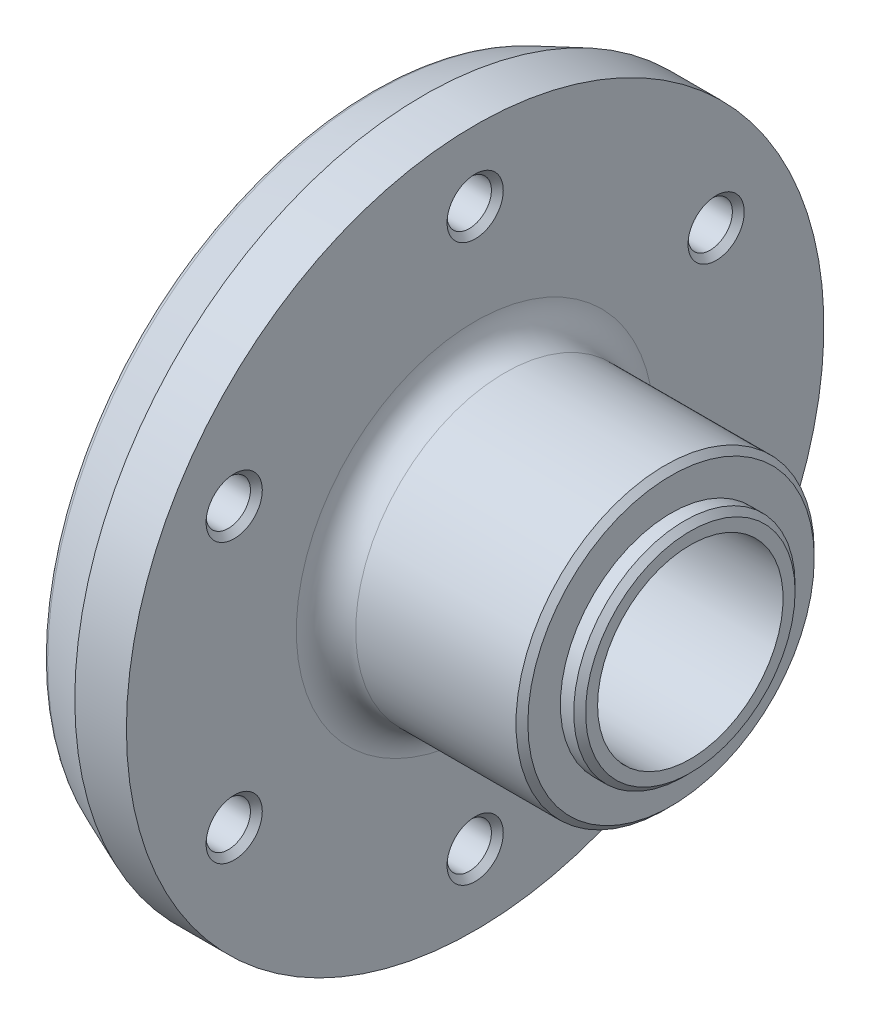
SolidWorks part; units mm, degrees
ref_plane "Front" through (0, 0, 0) normal (0, 0, 1) x (1, 0, 0)
ref_plane "Top" through (0, 0, 0) normal (0, 1, 0) x (1, 0, 0)
ref_plane "Right" through (0, 0, 0) normal (1, 0, 0) x (0, 0, -1)
ref_plane "Plane1" through (0, 0, 0) normal (0, 0, -1) x (-1, 0, 0)
sketch "Sketch1" plane through (0, 0, 0) normal (0, 0, -1) x (-1, 0, 0)
  line L0 (-55.88, 29.845) -> (-55.88, 0)
  line L1 (-55.88, 0) -> (-46.863, 0)
  line L2 (-46.863, 0) -> (-46.863, 27.94)
  line L3 (-46.863, 27.94) -> (-51.4621, 29.845)
  line L4 (-51.4621, 29.845) -> (-55.88, 29.845)
  line L5 (-55.88, 0) -> (-46.863, 0) construction
revolve "Revolve1" add sketch "Sketch1" angle 360 about L5 reverse direction yes
sketch "Sketch2" plane through (55.88, 0, 0) normal (1, 0, 0) x (0, 0, -1)
  circle A0 centre (0, 0) radius 12.7635
extrude "Boss-Extrude1" add sketch "Sketch2" along normal blind 16.764
sketch "Sketch3" plane through (72.644, 0, 0) normal (1, 0, 0) x (0, 0, -1)
  circle A0 centre (0, 0) radius 9.4742
extrude "Boss-Extrude2" add sketch "Sketch3" along normal blind 1.651
hole_wizard "5/8 (0.625) Diameter Hole1" positions "Sketch5" profile "Sketch4" hole size "5/8" standard "ANSI Inch"
sketch "Sketch5" plane through (46.863, 0, 0) normal (-1, 0, 0) x (0, 0, 1)
  point P0 (0, 0)
sketch "Sketch4" plane through (46.863, 0, 0) normal (0, 1, 0) x (0, 0, 1)
  line L0 (0, 0) -> (0, 27.432)
  line L1 (0, 27.432) -> (7.9375, 27.432)
  line L2 (7.9375, 27.432) -> (7.9375, 0)
  line L5 (7.9375, 0) -> (0, 0)
  line L11 (0, -6.35) -> (0, 107.95) construction
  dimension "Thru Hole Dia." = 15.875
  dimension "Thru Hole Depth" = 27.432
hole_wizard "#25 (0.1495) Diameter Hole1" positions "Sketch7" profile "Sketch6" hole size "#25" standard "ANSI Inch"
sketch "Sketch7" plane through (55.88, 0, 0) normal (1, 0, 0) x (0, 0, -1)
  point P0 (-20.6222, 11.9062)
  point P1 (20.6222, 11.9062)
  point P2 (20.6222, -11.9062)
  point P3 (0, -23.8125)
sketch "Sketch6" plane through (55.88, 11.9062, 20.6222) normal (0, 1, 0) x (0, 0, -1)
  line L0 (0, 0) -> (0, 9.017)
  line L1 (0, 9.017) -> (1.8986, 9.017)
  line L2 (1.8986, 9.017) -> (1.8986, 0)
  line L5 (1.8986, 0) -> (0, 0)
  line L11 (0, -6.35) -> (0, 107.95) construction
  dimension "Thru Hole Dia." = 3.7973
  dimension "Thru Hole Depth" = 9.017
hole_wizard "#25 (0.1495) Diameter Hole2" positions "Sketch9" profile "Sketch8" hole size "#25" standard "ANSI Inch"
sketch "Sketch9" plane through (46.863, 0, 0) normal (-1, 0, 0) x (0, 0, 1)
  point P0 (20.6222, -11.9062)
  point P1 (0, 23.8125)
sketch "Sketch8" plane through (46.863, -11.9062, 20.6222) normal (0, 1, 0) x (0, 0, 1)
  line L0 (0, 0) -> (0, 27.432)
  line L1 (0, 27.432) -> (1.8986, 27.432)
  line L2 (1.8986, 27.432) -> (1.8986, 0)
  line L5 (1.8986, 0) -> (0, 0)
  line L11 (0, -6.35) -> (0, 107.95) construction
  dimension "Thru Hole Dia." = 3.7973
  dimension "Thru Hole Depth" = 27.432
chamfer "Chamfer1" distance 0.508 angle 45 14 edges at (46.863, 11.9062, 18.7236) (46.863, -23.8125, -1.8986) (46.863, 11.9062, -22.5209) (55.88, 11.9062, 18.7236) (55.88, -11.9062, 18.7236) (55.88, 23.8125, -1.8986) (46.863, 23.8125, 1.8986) (55.88, 11.9062, -22.5209) (46.863, -11.9062, -22.5209) (55.88, -11.9062, -22.5209) (74.295, 0, -9.4742) (72.644, 0, -12.7635) (55.88, -23.8125, -1.8986) (46.863, -11.9062, 22.5209)
chamfer "Chamfer2" distance 0.2773 angle 70 1 edges at (46.863, 0, 7.9375) first distance on face at (46.863, 11.9062, 23.0289)
fillet "Fillet1" radius 1.016 1 edges at (46.863, 0, 27.94) tangent propagation no
fillet "Fillet2" radius 2.54 1 edges at (55.88, 0, -12.7635) tangent propagation no
